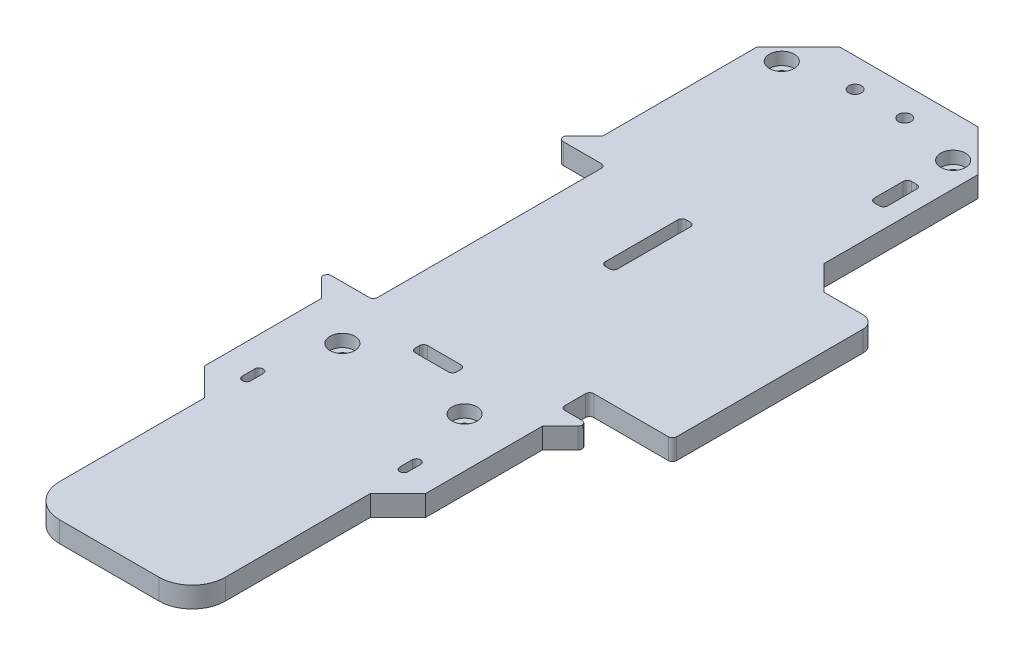
SolidWorks part; units mm, degrees
ref_plane "Front Plane" through (0, 0, 0) normal (0, 0, 1) x (1, 0, 0)
ref_plane "Top Plane" through (0, 0, 0) normal (0, 1, 0) x (1, 0, 0)
ref_plane "Right Plane" through (0, 0, 0) normal (1, 0, 0) x (0, 0, -1)
sketch "Sketch1" plane through (0, 0, 0) normal (0, 1, 0) x (1, 0, 0)
  line L0 (-26.6834, 28) -> (26.6834, 28)
  line L1 (-45.1, -28) -> (45.1, -28)
  line L2 (-45.1, -28) -> (-45.1, 28)
  line L3 (-45.1, 28) -> (45.1, 28)
  line L4 (45.1, -28) -> (45.1, 28)
  line L5 (-45.1, -28) -> (45.1, 28) construction
  line L6 (-45.1, 28) -> (45.1, -28) construction
  line L15 (-35.8524, 28) -> (35.8524, 28)
  line L19 (-26.6834, 28) -> (-26.6834, 71.16)
  line L20 (26.6834, 28) -> (26.6834, 71.16)
  line L21 (-26.6834, 71.16) -> (-16.6834, 81.16)
  line L22 (-16.6834, 81.16) -> (16.6834, 81.16)
  line L23 (16.6834, 81.16) -> (26.6834, 71.16)
  line L24 (-32.6834, -28) -> (32.6834, -28)
  line L25 (32.6834, -28) -> (26.6834, -34)
  line L26 (26.6834, -34) -> (26.6834, -62.1566)
  line L27 (26.6834, -62.1566) -> (20, -68.84)
  line L28 (20, -68.84) -> (-20, -68.84)
  line L29 (-20, -68.84) -> (-26.6834, -62.1566)
  line L30 (-26.6834, -62.1566) -> (-26.6834, -34)
  line L31 (-26.6834, -34) -> (-32.6834, -28)
  line L32 (-32.6834, 28) -> (-26.6834, 34)
  line L33 (26.6834, 34) -> (32.6834, 28)
  line L34 (0, -68.84) -> (0, -35.8847) construction
  line L39 (-45.1, 28) -> (-20.1, 28)
  line L40 (-45.1, 28) -> (-45.1, -28)
  line L41 (-45.1, -28) -> (-20.1, -28)
  line L42 (-20.1, 28) -> (-20.1, -28)
  line L43 (45.1, -28) -> (25.1, -28)
  line L44 (45.1, -28) -> (45.1, -21)
  line L45 (45.1, -21) -> (25.1, -21)
  line L46 (25.1, -28) -> (25.1, -21)
  line L48 (-0.1, 26.5) -> (2.9, 26.5)
  line L49 (-0.1, 26.5) -> (-0.1, 7)
  line L50 (-0.1, 7) -> (2.9, 7)
  line L51 (2.9, 26.5) -> (2.9, 7)
  line L52 (-20, -68.84) -> (20, -68.84)
  line L53 (-20, -68.84) -> (-20, -111.84)
  line L54 (-20, -111.84) -> (20, -111.84)
  line L55 (20, -68.84) -> (20, -111.84)
  circle A0 centre (-20.6834, 71.16) radius 1.525
  circle A1 centre (20.6834, 71.16) radius 1.525
  circle A2 centre (-14.75, -40.84) radius 1.525
  circle A3 centre (14.75, -40.84) radius 1.525
  point P0 (0, 0)
  point P29 (0, -28)
  dimension "D18" = 3.05
  dimension "D20" = 3.05
  dimension "D25" = 3.05
  dimension "D1" = 56
  dimension "D2" = 90.2
  dimension "D3" = 25
  dimension "D4" = 6
  dimension "D5" = 6
  dimension "D6" = 20
  dimension "D7" = 53.3668
  dimension "D8" = 43.16
  dimension "D9" = 33.3668
  dimension "D10" = 53.16
  dimension "D11" = 40.84
  dimension "D12" = 53.3668
  dimension "D13" = 40
  dimension "D14" = 65.3668
  dimension "D15" = 28.1566
  dimension "D16" = 6
  dimension "D17" = 6
  dimension "D19" = 7
  dimension "D21" = 6
  dimension "D22" = 6
  dimension "D23" = 5.25
  dimension "D24" = 28
  dimension "D26" = 45
  dimension "D27" = 3
  dimension "D28" = 1.5
  dimension "D29" = 19.5
  dimension "D30" = 43
extrude "Boss-Extrude1" add sketch "Sketch1" along normal blind 5 contours L31 L30 L29 L28 L27 L26 L25 L1 | L23 L22 L21 L19 L0 L3 L20 | L3 L19 | L33 L20 L3 | L15 L42 L24 L1 L4 L3 L43 L46 L45 L44 | L55 L28 L53 L54 region at (0, 0, -53.6371) region at (-28.6834, 0, -30) region at (11.7717, 0, -0.7096) region at (28.6834, 0, -30) region at (0, 0, 47.787) region at (0, 0, 90.34)
fillet "Fillet4" radius 3 1 edges at (45.1, 2.5, -28)
fillet "Fillet5" radius 1 12 edges at (-32.6834, 2.5, -28) (-32.6834, 2.5, 28) (32.6834, 2.5, 28) (45.1, 2.5, 21) (25.1, 2.5, 21) (25.1, 2.5, 28) (-20.1, 2.5, 28) (-20.1, 2.5, -28) (-0.1, 2.5, -7) (2.9, 2.5, -7) (2.9, 2.5, -26.5) (-0.1, 2.5, -26.5)
sketch "Sketch4" plane through (0, 5, 0) normal (0, 1, 0) x (1, 0, 0)
  circle A0 centre (-20.6834, 71.16) radius 3
  circle A1 centre (20.6834, 71.16) radius 3
  circle A2 centre (-14.75, -40.84) radius 3
  circle A3 centre (14.75, -40.84) radius 3
  dimension "D1" = 6
  dimension "D2" = 6
  dimension "D3" = 6
  dimension "D4" = 6
extrude "Cut-Extrude1" cut sketch "Sketch4" against normal blind 3
fillet "Fillet6" radius 8 2 edges at (20, 2.5, 111.84) (-20, 2.5, 111.84)
sketch "Sketch5" plane through (20, 0, 0) normal (1, 0, 0) x (0, 0, -1)
  line L0 (-103.84, 5) -> (-103.84, 0) construction
  line L1 (-68.84, 0) -> (-103.84, 0) construction
  circle A0 centre (-83.11, -17) radius 19.7272
  point P7 (-83.11, 2.7272)
  dimension "D3" = 39.4544
  dimension "D1" = 20.73
  dimension "D2" = 17
ref_plane "Plane1" through (12.2, 0, 0) normal (1, 0, 0) x (0, 0, -1)
sketch "Sketch6" plane through (12.2, 0, 0) normal (1, 0, 0) x (0, 0, -1)
  circle A0 centre (-83.11, -17) radius 19.7272
extrude "Cut-Extrude2" cut sketch "Sketch6" against normal blind 6
sketch "Sketch8" plane through (0, 0, -81.16) normal (0, 0, -1) x (-1, 0, 0)
  line L0 (16.6834, 5) -> (16.6834, 0) construction
  line L1 (16.6834, 0) -> (-16.6834, 0) construction
  circle A0 centre (0.1634, -7.9) radius 8.5
  dimension "D3" = 17
  dimension "D1" = 16.52
  dimension "D2" = 7.9
ref_plane "Plane2" through (0, 0, -46.16) normal (0, 0, -1) x (-1, 0, 0)
sketch "Sketch9" plane through (0, 0, -46.16) normal (0, 0, -1) x (-1, 0, 0)
  circle A0 centre (0.1634, -7.9) radius 9
  dimension "D1" = 18
extrude "Cut-Extrude3" cut sketch "Sketch9" against normal blind 8.5
sketch "Sketch11" plane through (0, 5, 0) normal (0, 1, 0) x (1, 0, 0)
  line L1 (-18, -60.7193) -> (-20, -60.7193)
  line L2 (-18, -60.7193) -> (-18, -55.7193)
  line L3 (-18, -55.7193) -> (-20, -55.7193)
  line L4 (-20, -60.7193) -> (-20, -55.7193)
  line L5 (18, -60.7193) -> (20, -60.7193)
  line L6 (18, -60.7193) -> (18, -55.7193)
  line L7 (18, -55.7193) -> (20, -55.7193)
  line L8 (20, -60.7193) -> (20, -55.7193)
  line L10 (-20, -68.84) -> (-20, -103.84) construction
  line L11 (20, -68.84) -> (20, -103.84) construction
  line L13 (-5, -34) -> (5, -34)
  line L14 (-5, -34) -> (-5, -31)
  line L15 (-5, -31) -> (5, -31)
  line L16 (5, -34) -> (5, -31)
  line L17 (-5, -34) -> (5, -31) construction
  line L18 (-5, -31) -> (5, -34) construction
  point P12 (0, -32.5)
  point P20 (0, -34)
  dimension "D1" = 5
  dimension "D2" = 2
  dimension "D3" = 5
  dimension "D4" = 2
  dimension "D5" = 10
  dimension "D6" = 3
extrude "Cut-Extrude4" cut sketch "Sketch11" against normal blind 6
fillet "Fillet7" radius 1 12 edges at (-18, 2.5, 55.7193) (-20, 2.5, 55.7193) (-18, 2.5, 60.7193) (-20, 2.5, 60.7193) (20, 2.5, 60.7193) (18, 2.5, 60.7193) (18, 2.5, 55.7193) (20, 2.5, 55.7193) (5, 2.5, 31) (5, 2.5, 34) (-5, 2.5, 34) (-5, 2.5, 31)
sketch "Sketch13" plane through (0, 5, 0) normal (0, 1, 0) x (1, 0, 0)
  line L0 (-16.6834, 81.16) -> (16.6834, 81.16) construction
  line L2 (19.0584, 52.7265) -> (22.3084, 52.7265)
  line L3 (19.0584, 52.7265) -> (19.0584, 61.7265)
  line L4 (19.0584, 61.7265) -> (22.3084, 61.7265)
  line L5 (22.3084, 52.7265) -> (22.3084, 61.7265)
  line L6 (19.0584, 52.7265) -> (22.3084, 61.7265) construction
  line L7 (19.0584, 61.7265) -> (22.3084, 52.7265) construction
  circle A0 centre (-6, 74.16) radius 1.525
  circle A1 centre (6, 74.16) radius 1.525
  point P4 (20.6834, 57.2265)
  point P12 (20.6834, 71.16)
  point P13 (0, 0)
  point P14 (20.6834, 61.7265)
  dimension "D1" = 3.05
  dimension "D2" = 3.05
  dimension "D3" = 6
  dimension "D4" = 12
  dimension "D5" = 7
  dimension "D6" = 9
  dimension "D7" = 3.25
extrude "Cut-Extrude5" cut sketch "Sketch13" against normal blind 6
fillet "Fillet8" radius 1 4 edges at (22.3084, 2.5, -52.7265) (19.0584, 2.5, -52.7265) (22.3084, 2.5, -61.7265) (19.0584, 2.5, -61.7265)
